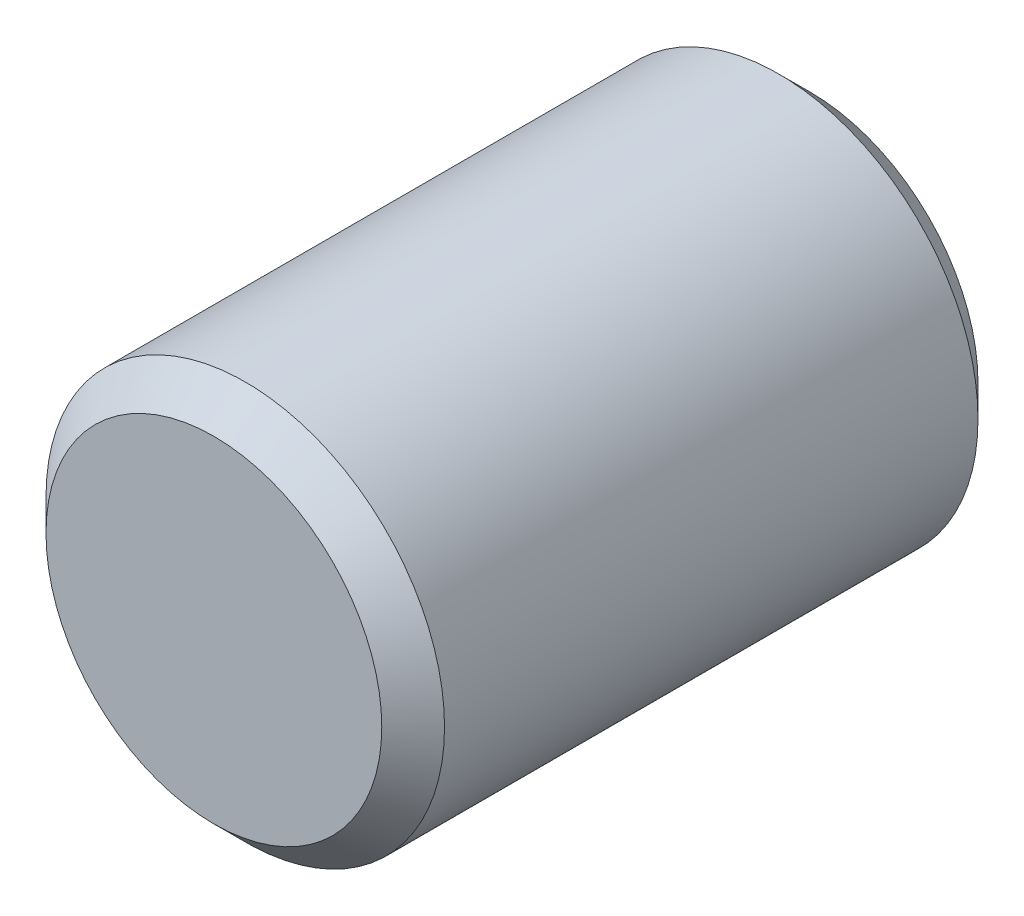
SolidWorks part; units mm, degrees
ref_plane "Front Plane" through (0, 0, 0) normal (0, 0, 1) x (1, 0, 0)
ref_plane "Top Plane" through (0, 0, 0) normal (0, 1, 0) x (1, 0, 0)
ref_plane "Right Plane" through (0, 0, 0) normal (1, 0, 0) x (0, 0, -1)
sketch "Sketch1" plane through (0, 0, 0) normal (0, 0, 1) x (1, 0, 0)
  circle A0 centre (0, 0) radius 3.175
  dimension "D1" = 6.35
extrude "Boss-Extrude1" add sketch "Sketch1" along normal blind 4.75 and the other way blind 4.75
chamfer "Chamfer1" distance 0.5 angle 45 2 edges at (3.175, 0, -4.75) (3.175, 0, 4.75)
